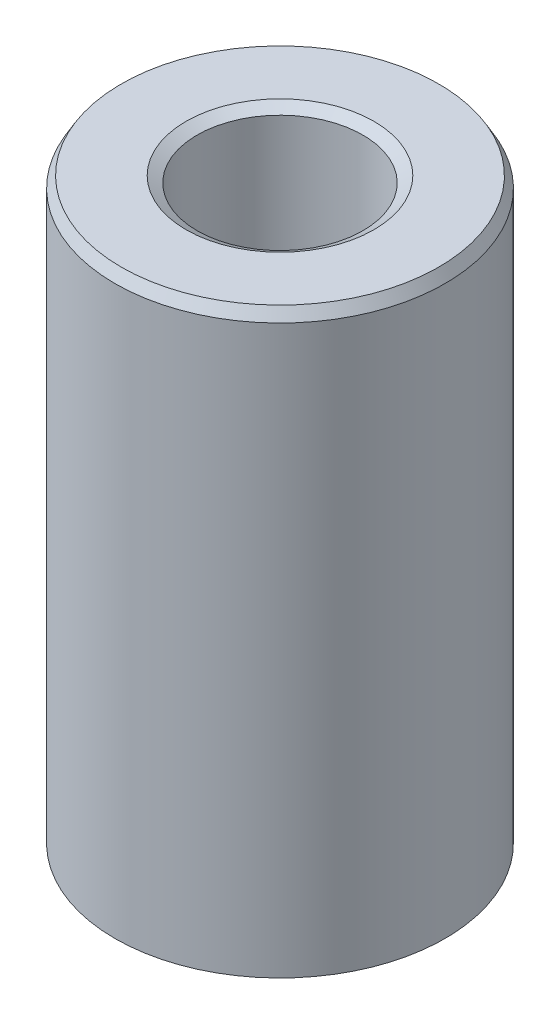
SolidWorks part; units mm, degrees
ref_plane "Front Plane" through (0, 0, 0) normal (0, 0, 1) x (1, 0, 0)
ref_plane "Top Plane" through (0, 0, 0) normal (0, 1, 0) x (1, 0, 0)
ref_plane "Right Plane" through (0, 0, 0) normal (1, 0, 0) x (0, 0, -1)
sketch "Sketch1" plane through (0, 0, 0) normal (0, 1, 0) x (1, 0, 0)
  circle A0 centre (0, 0) radius 7.5
  dimension "SLEEVE_OD" = 15
extrude "Boss-Extrude1" add sketch "Sketch1" along normal blind 26.561
sketch "Sketch2" plane through (0, 0, 0) normal (0, 1, 0) x (1, 0, 0)
  circle A0 centre (0, 0) radius 3.7668
  dimension "BORE_D" = 7.5336
extrude "Cut-Extrude1" cut sketch "Sketch2" along normal through all
chamfer "Chamfer1" distance 0.5013 angle 30 4 edges at (0, 26.561, 3.7668) (0, 0, 3.7668) (0, 0, 7.5) (0, 26.561, 7.5) first distance on face at (0, 26.561, 3.7668) first distance on face at (0, 0, 3.7668) first distance on face at (0, 26.561, 7.5)
